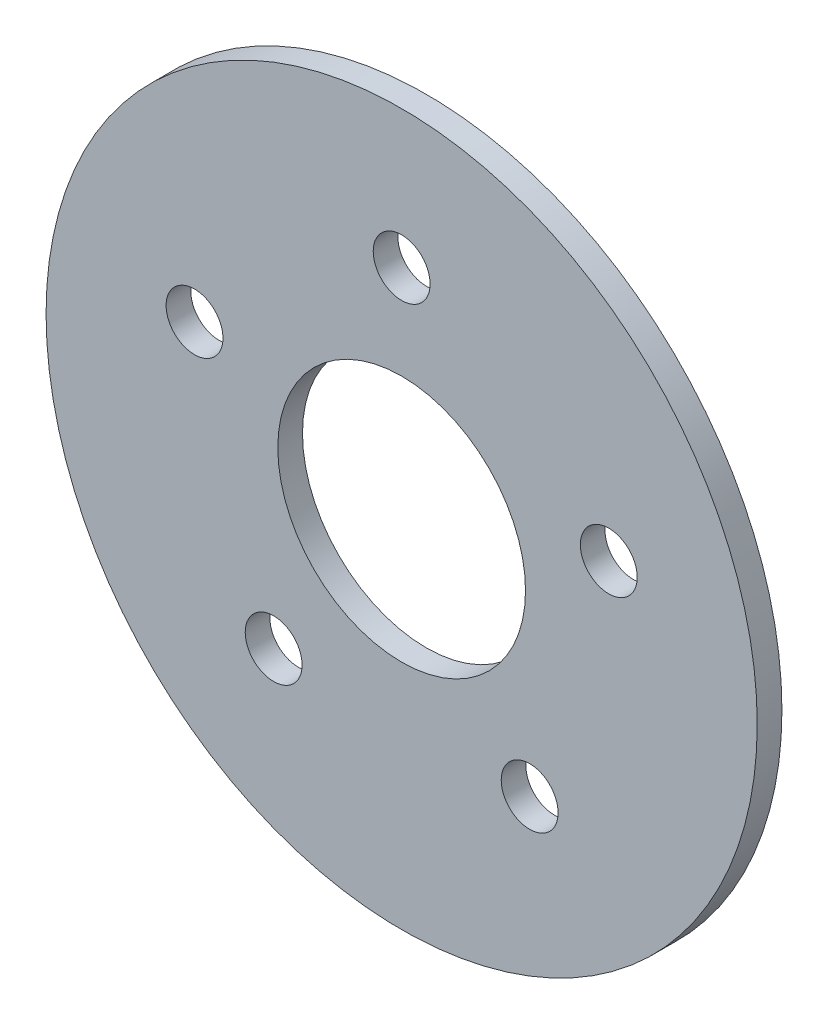
SolidWorks part; units mm, degrees
ref_plane "Front Plane" through (0, 0, 0) normal (0, 0, 1) x (1, 0, 0)
ref_plane "Top Plane" through (0, 0, 0) normal (0, 1, 0) x (1, 0, 0)
ref_plane "Right Plane" through (0, 0, 0) normal (1, 0, 0) x (0, 0, -1)
sketch "Sketch1" plane through (0, 0, -15.24) normal (0, 0, -1) x (-1, 0, 0)
  circle A0 centre (0, 0) radius 7.9629 construction
  circle A1 centre (0, 0) radius 7.9629
  circle A2 centre (0, 0) radius 22.86
  circle A3 centre (13.3148, 4.3262) radius 1.8288 construction
  circle A4 centre (8.229, -11.3262) radius 1.8288 construction
  circle A5 centre (-8.229, -11.3262) radius 1.8288 construction
  circle A6 centre (-13.3148, 4.3262) radius 1.8288 construction
  circle A7 centre (0, 14) radius 1.8288 construction
  circle A8 centre (13.3148, 4.3262) radius 1.8288
  circle A9 centre (8.229, -11.3262) radius 1.8288
  circle A10 centre (-8.229, -11.3262) radius 1.8288
  circle A11 centre (-13.3148, 4.3262) radius 1.8288
  circle A12 centre (0, 14) radius 1.8288
  dimension "D1" = 45.72
extrude "Boss-Extrude1" add sketch "Sketch1" along normal blind 1.5875
